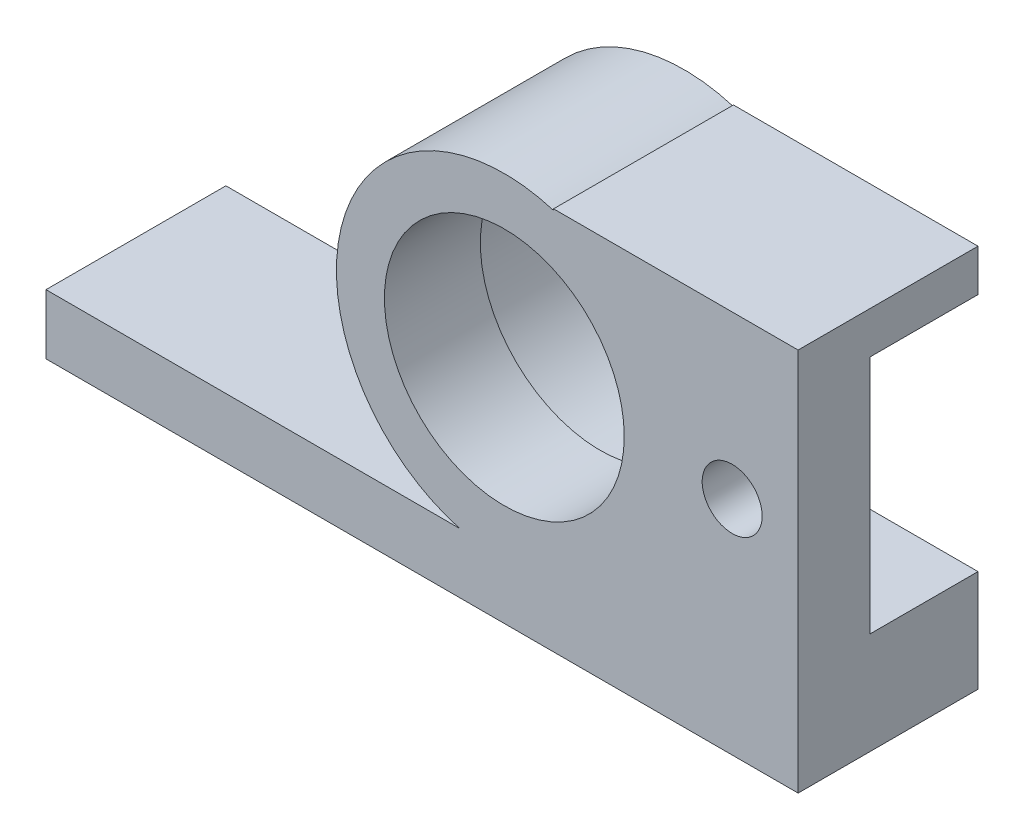
SolidWorks part; units mm, degrees
ref_plane "前视基准面" through (0, 0, 0) normal (0, 0, 1) x (1, 0, 0)
ref_plane "上视基准面" through (0, 0, 0) normal (0, 1, 0) x (1, 0, 0)
ref_plane "右视基准面" through (0, 0, 0) normal (1, 0, 0) x (0, 0, -1)
sketch "草图1" plane through (0, 0, 0) normal (0, 0, 1) x (1, 0, 0)
  line L1 (20, -10) -> (-20, -10)
  line L2 (20, -10) -> (20, 10)
  line L3 (20, 10) -> (-20, 10)
  line L4 (-20, -10) -> (-20, 10)
  line L5 (20, -10) -> (-20, 10) construction
  line L6 (20, 10) -> (-20, -10) construction
  point P0 (0, 0)
  dimension "D1" = 40
  dimension "D2" = 20
extrude "凸台-拉伸1" add sketch "草图1" along normal blind 6
sketch "草图2" plane through (0, 0, 6) normal (0, 0, 1) x (1, 0, 0)
  line L0 (20, -10) -> (20, 10) construction
  circle A0 centre (10, 0) radius 2.5
  circle A1 centre (-1, 0) radius 2.5
  circle A2 centre (-12, 0) radius 2.5
  dimension "D1" = 10
  dimension "D2" = 5
  dimension "D3" = 3
extrude "切除-拉伸1" cut sketch "草图2" against normal through all
sketch "草图3" plane through (0, 0, 6) normal (0, 0, 1) x (1, 0, 0)
  line L0 (20, 13.5) -> (20, 10)
  line L1 (20, -13.5) -> (-26.894, -13.5)
  line L3 (20, 13.5) -> (-26.894, 13.5)
  line L4 (-20, 10) -> (-20, -10)
  line L5 (-20, -10) -> (20, -10)
  line L6 (20, -10) -> (20, 10)
  line L7 (20, 10) -> (-20, 10)
  line L8 (-20, 10) -> (-20, -10)
  line L9 (-20, -10) -> (20, -10)
  line L10 (20, -10) -> (20, 10)
  line L11 (20, 10) -> (-20, 10)
  line L12 (-26.894, -13.5) -> (-26.894, 13.5)
  line L13 (20, -10.0394) -> (-26.894, 13.5) construction
  line L14 (20, 10.0394) -> (-26.894, -13.5) construction
  line L15 (20, -10) -> (20, -13.5)
  circle A0 centre (-31, 0) radius 11
  circle A1 centre (-31, 0) radius 14
  point P2 (0, 0)
  line M10 (-20, 10) -> (-20, -10)
  line M11 (-20, -10) -> (20, -10)
  line M13 (20, 10) -> (-20, 10)
  dimension "D3" = 22
  dimension "D4" = 28
  dimension "D2" = 3.5
  dimension "D1" = 0
extrude "凸台-拉伸2" add sketch "草图3" against normal blind 15 contours L3 A1 L1 L12 A0 | A1 L1 L15 M11 M10 | L1 A1 L8 A0 L12 | L8 A1 L3 L12 A0 | L8 A1 | A1 L0 L3 M10 M13 region at (-1.9449, 11.7771, 6) region at (-1.9449, -11.7771, 6) region at (-23.0173, 9.0328, 6) region at (-27.2274, 11.7946, 6) region at (-18.7882, 0, 6) region at (-23.0173, -9.0328, 6)
sketch "草图5" plane through (0, 0, 6) normal (0, 0, 1) x (1, 0, 0)
  circle A0 centre (-31, 0) radius 10
  circle A1 centre (-31, 0) radius 11 construction
  circle A2 centre (-31, 0) radius 11
  dimension "D1" = 20
extrude "凸台-拉伸3" add sketch "草图5" against normal blind 8
sketch "草图6" plane through (0, 0, 6) normal (0, 0, 1) x (1, 0, 0)
  circle A0 centre (-31, 0) radius 8.5
  circle A1 centre (-31, 0) radius 10 construction
  circle A2 centre (-31, 0) radius 10
  dimension "D1" = 17
sketch "草图8" plane through (0, 0, 6) normal (0, 0, 1) x (1, 0, 0)
  line L0 (20, -13.5) -> (20, 13.5) construction
  line L1 (20, -13.5) -> (-26.894, -13.5) construction
  line L2 (20, 13.5) -> (-26.894, 13.5) construction
  line L3 (20, -13.5) -> (20, 13.5)
  line L4 (20, -13.5) -> (-26.894, -13.5)
  line L5 (20, 13.5) -> (-26.894, 13.5)
  line L6 (-45, -14) -> (-26.894, -13.5)
  line L7 (-45, -14) -> (-239, -14)
  line L8 (-45, -14) -> (-45, 14)
  line L9 (-45, 14) -> (-239, 14)
  line L10 (-239, -14) -> (-239, 14)
  line L11 (-45, -14) -> (-239, 14) construction
  line L12 (-45, 14) -> (-239, -14) construction
  line L13 (-45, 14) -> (-26.894, 13.3843)
  line L14 (-12, 0) -> (-31, 0)
  arc A0 (-26.894, 13.3843) -> (-26.894, -13.3843) centre (-31, 0) ccw construction
  arc A1 (-26.894, 13.3843) -> (-26.894, -13.3843) centre (-31, 0) ccw
  point P6 (-142, 0)
  dimension "D1" = 28
  dimension "D2" = 194
  dimension "D3" = 14
sketch "草图9" plane through (0, -13.5, 0) normal (0, -1, 0) x (1, 0, 0)
  circle A0 centre (10.5344, 0) radius 5.2388
sketch "草图10" plane through (20, 0, 0) normal (1, 0, 0) x (0, 0, -1)
  line L1 (9, -13.5) -> (-6, -13.5)
  line L2 (9, -13.5) -> (9, -18.5)
  line L3 (9, -18.5) -> (-6, -18.5)
  line L4 (-6, -13.5) -> (-6, -18.5)
  dimension "D1" = 5
extrude "凸台-拉伸4" add sketch "草图10" against normal blind 500
sketch "草图11" plane through (0, 0, -9) normal (0, 0, -1) x (-1, 0, 0)
  line L1 (22.0371, -11.3638) -> (33.5283, -11.3638)
  line L2 (22.0371, -11.3638) -> (22.0371, -16.4864)
  line L3 (22.0371, -16.4864) -> (33.5283, -16.4864)
  line L4 (33.5283, -11.3638) -> (33.5283, -16.4864)
extrude "凸台-拉伸5" add sketch "草图11" against normal through all
sketch "草图12" plane through (0, 0, 6) normal (0, 0, 1) x (1, 0, 0)
  line L0 (-12, 0) -> (-1, 0) construction
  line L1 (-6.5, 0) -> (-6.5, 13.5) construction
  line L2 (20, 13.5) -> (-26.894, 13.5) construction
  line L4 (-6.5, 13.5) -> (20, 13.5)
  line L5 (-6.5, 13.5) -> (-6.5, -18.5)
  line L6 (-6.5, -18.5) -> (20, -18.5)
  line L7 (20, 13.5) -> (20, -18.5)
extrude "切除-拉伸2" cut sketch "草图12" against normal through all
sketch "草图13" plane through (0, -18.5, 0) normal (0, -1, 0) x (1, 0, 0)
  line L0 (-69.2198, 6) -> (-69.2198, -9.0491)
  line L1 (-480, 6) -> (-6.5, 6) construction
  line L2 (-69.2198, 131.4142) -> (-69.2198, -238.5858) construction
sketch "草图14" plane through (0, -18.5, 0) normal (0, -1, 0) x (1, 0, 0)
  line L1 (-69.2198, -9.0491) -> (-494.0275, -9.0491)
  line L2 (-69.2198, -9.0491) -> (-69.2198, 12.8124)
  line L3 (-69.2198, 12.8124) -> (-494.0275, 12.8124)
  line L4 (-494.0275, -9.0491) -> (-494.0275, 12.8124)
extrude "切除-拉伸3" cut sketch "草图14" against normal through all
